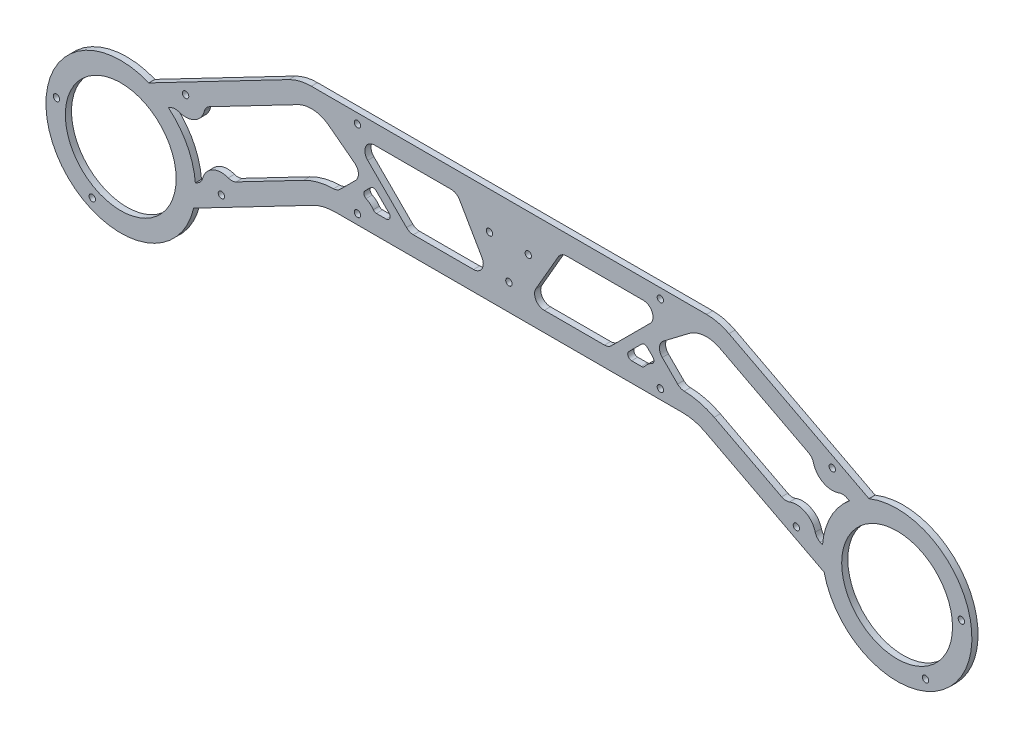
SolidWorks part; units mm, degrees
material "6061-T6 (SS)"
ref_plane "Front Plane" through (0, 0, 0) normal (0, 0, 1) x (1, 0, 0)
ref_plane "Top Plane" through (0, 0, 0) normal (0, 1, 0) x (1, 0, 0)
ref_plane "Right Plane" through (0, 0, 0) normal (1, 0, 0) x (0, 0, -1)
sketch "Sketch1" plane through (0, 0, 0) normal (0, 0, 1) x (1, 0, 0)
  line L0 (-200, -104.1134) -> (0, 0) construction
  line L1 (0, 0) -> (200, -104.1134) construction
  line L2 (-221.4586, -97.3475) -> (-193.2341, -82.6548) construction
  line L3 (-113.3558, -30.8247) -> (-235.4371, -94.3763)
  line L4 (-237.5634, -101.1201) -> (-219.0935, -136.6005)
  line L5 (-212.3497, -138.7268) -> (-101.1208, -80.8247)
  line L6 (-101.8121, -28) -> (101.8121, -28)
  line L7 (0, -28) -> (0, -78) construction
  line L8 (89.5771, -78) -> (-89.5771, -78)
  line L9 (113.3558, -30.8247) -> (235.4371, -94.3763)
  line L10 (237.5634, -101.1201) -> (219.0935, -136.6005)
  line L11 (212.3497, -138.7268) -> (101.1208, -80.8247)
  circle A1 centre (-200, -104.1134) radius 16.05
  circle A2 centre (-221.4586, -97.3475) radius 1.65
  circle A3 centre (-193.2341, -82.6548) radius 1.65
  circle A4 centre (-178.5414, -110.8793) radius 1.65
  circle A5 centre (-206.7659, -125.572) radius 1.65
  arc A6 (-235.4371, -94.3763) -> (-237.5634, -101.1201) centre (-233.1284, -98.8113) ccw
  arc A7 (-219.0935, -136.6005) -> (-212.3497, -138.7268) centre (-214.6584, -134.2918) ccw
  circle A8 centre (0, 0) radius 25 construction
  circle A11 centre (-200, -104.1134) radius 33.55 construction
  circle A12 centre (206.7659, -125.572) radius 1.65
  circle A13 centre (221.4586, -97.3475) radius 1.65
  circle A14 centre (193.2341, -82.6548) radius 1.65
  circle A15 centre (178.5414, -110.8793) radius 1.65
  circle A16 centre (200, -104.1134) radius 16.05
  arc A17 (235.4371, -94.3763) -> (237.5634, -101.1201) centre (233.1284, -98.8113) cw
  arc A18 (219.0935, -136.6005) -> (212.3497, -138.7268) centre (214.6584, -134.2918) cw
  circle A19 centre (-10, -47.2265) radius 1.65
  circle A20 centre (10, -47.2265) radius 1.65
  circle A21 centre (0, -64.547) radius 1.65
  arc A22 (101.1208, -80.8247) -> (89.5771, -78) centre (89.5771, -103) ccw
  arc A23 (113.3558, -30.8247) -> (101.8121, -28) centre (101.8121, -53) ccw
  arc A24 (-113.3558, -30.8247) -> (-101.8121, -28) centre (-101.8121, -53) cw
  arc A25 (-101.1208, -80.8247) -> (-89.5771, -78) centre (-89.5771, -103) cw
  point P17 (-200, -104.1134)
  point P27 (0, -53)
  point P28 (0, -25)
  point P53 (0, -53)
  point P54 (95.6946, -78)
  point P57 (107.9295, -28)
  point P60 (-107.9295, -28)
  point P63 (-95.6946, -78)
  dimension "D1" = 400
  dimension "D3" = 32.1
  dimension "D5" = 3.3
  dimension "D7" = 50
  dimension "D10" = 5
  dimension "D11" = 3.3
  dimension "D12" = 67.1
  dimension "D14" = 3
  dimension "D16" = 25
  dimension "D2" = 125
  dimension "D6" = 45
  dimension "D8" = 3
  dimension "D9" = 50
  dimension "D13" = 50
  dimension "D15" = 20
  dimension "D4" = 4
extrude "Base" add sketch "Sketch1" along normal blind 3.175
sketch "Sketch3" plane through (0, 0, 3.175) normal (0, 0, 1) x (1, 0, 0)
  line L1 (-89.5771, -78) -> (89.5771, -78) construction
  line L2 (-228.3285, -118.8603) -> (-185.7635, -96.7023) construction
  line L3 (101.8121, -28) -> (-101.8121, -28) construction
  line L4 (-237.5634, -101.1201) -> (-219.0935, -136.6005) construction
  line L5 (0, -28) -> (0, -78) construction
  circle A0 centre (-214.6584, -134.2918) radius 1.65
  circle A1 centre (-148.1326, -99.6606) radius 1.65
  circle A2 centre (-78.0312, -73) radius 1.65
  circle A3 centre (-78.0312, -33) radius 1.65
  circle A4 centre (-200, -104.1134) radius 16.05 construction
  circle A5 centre (-166.6026, -64.1802) radius 1.65
  circle A6 centre (-233.1284, -98.8113) radius 1.65
  circle A7 centre (233.1284, -98.8113) radius 1.65
  circle A8 centre (166.6026, -64.1802) radius 1.65
  circle A9 centre (78.0312, -33) radius 1.65
  circle A10 centre (78.0312, -73) radius 1.65
  circle A11 centre (148.1326, -99.6606) radius 1.65
  circle A12 centre (214.6584, -134.2918) radius 1.65
  dimension "D1" = 3.3
  dimension "D3" = 75
  dimension "D6" = 5
  dimension "D4" = 5
  dimension "D5" = 75
  dimension "D2" = 2
extrude "Strut Holes" cut sketch "Sketch3" against normal through all
sketch "Sketch4" plane through (0, 0, 0) normal (0, 0, -1) x (-1, 0, 0)
  line L0 (-166.7326, -103.7062) -> (-160.3585, -100.3881)
  line L1 (-101.1208, -80.8247) -> (-212.3497, -138.7268) construction
  line L2 (-140.5243, -90.063) -> (-105.7383, -71.9546)
  line L3 (-86.9223, -66.5452) -> (-79.0095, -58.6325)
  line L4 (-79.5169, -51.1182) -> (-92.7277, -41.0638)
  line L5 (-180.585, -77.0959) -> (-174.2109, -73.7777)
  line L6 (-235.4371, -94.3763) -> (-113.3558, -30.8247) construction
  line L7 (-154.3768, -63.4527) -> (-108.7383, -39.6948)
  line L8 (89.5771, -78) -> (-89.5771, -78) construction
  line L9 (-68.2844, -68) -> (-63.1994, -68)
  line L10 (-61.7852, -64.5858) -> (-68.4242, -57.9467)
  line L11 (-71.2527, -57.9467) -> (-74.1321, -60.8262)
  line L12 (-25.4306, -40.5) -> (-13.8835, -60.5)
  line L13 (-18.2137, -68) -> (-49.2288, -68)
  line L14 (-52.7643, -66.5355) -> (-72.7643, -46.5355)
  line L15 (-69.2288, -38) -> (-29.7607, -38)
  line L16 (-101.8121, -28) -> (101.8121, -28) construction
  line L17 (0, -28) -> (0, -78) construction
  line L18 (52.7643, -66.5355) -> (72.7643, -46.5355)
  line L19 (18.2137, -68) -> (49.2288, -68)
  line L20 (25.4306, -40.5) -> (13.8835, -60.5)
  line L21 (69.2288, -38) -> (29.7607, -38)
  line L22 (68.2844, -68) -> (63.1994, -68)
  line L23 (61.7852, -64.5858) -> (68.4242, -57.9467)
  line L24 (71.2527, -57.9467) -> (74.1321, -60.8262)
  line L25 (154.3768, -63.4527) -> (108.7383, -39.6948)
  line L26 (180.585, -77.0959) -> (174.2109, -73.7777)
  line L27 (166.7326, -103.7062) -> (160.3585, -100.3881)
  line L28 (140.5243, -90.063) -> (105.7383, -71.9546)
  line L29 (86.9223, -66.5452) -> (79.0095, -58.6325)
  line L30 (79.5169, -51.1182) -> (92.7277, -41.0638)
  arc A0 (-182.112, -88.1128) -> (-176.6329, -98.638) centre (-200, -104.1134) cw
  arc A1 (-174.0237, -101.958) -> (-172.208, -103.1405) centre (-178.5414, -110.8793) cw
  arc A2 (-183.3349, -84.0711) -> (-183.2622, -81.9056) centre (-193.2341, -82.6548) ccw
  arc A3 (-157.8223, -97.1889) -> (-144.5996, -90.3055) centre (-148.1326, -99.6606) cw
  arc A4 (-105.7383, -71.9546) -> (-90.3477, -68.0085) centre (-89.5771, -103) cw
  arc A5 (-89.5771, -78) -> (-101.1208, -80.8247) centre (-89.5771, -103) ccw construction
  arc A6 (-170.1356, -73.5353) -> (-156.9129, -66.6519) centre (-166.6026, -64.1802) ccw
  arc A7 (-108.7383, -39.6948) -> (-92.7277, -41.0638) centre (-101.8121, -53) cw
  arc A8 (-101.8121, -28) -> (-113.3558, -30.8247) centre (-101.8121, -53) ccw construction
  arc A9 (-69.9089, -67.1667) -> (-73.6035, -64.0337) centre (-78.0312, -73) ccw
  circle A10 centre (-10, -47.2265) radius 10 construction
  circle A11 centre (0, -64.547) radius 10 construction
  arc A12 (-156.9129, -66.6519) -> (-154.3768, -63.4527) centre (-152.068, -67.8878) cw
  arc A13 (-174.2109, -73.7777) -> (-170.1356, -73.5353) centre (-171.9022, -78.2128) cw
  arc A14 (-183.2622, -81.9056) -> (-180.585, -77.0959) centre (-178.2763, -81.5309) cw
  arc A15 (-182.112, -88.1128) -> (-183.3349, -84.0711) centre (-178.3853, -84.7793) cw
  arc A16 (-176.6329, -98.638) -> (-174.0237, -101.958) centre (-171.7648, -97.4973) ccw
  arc A17 (-172.208, -103.1405) -> (-166.7326, -103.7062) centre (-169.0413, -99.2712) ccw
  arc A18 (-160.3585, -100.3881) -> (-157.8223, -97.1889) centre (-162.6672, -95.953) ccw
  arc A19 (-144.5996, -90.3055) -> (-140.5243, -90.063) centre (-142.833, -85.628) ccw
  arc A20 (-79.0095, -58.6325) -> (-79.5169, -51.1182) centre (-82.545, -55.0969) ccw
  arc A21 (-90.3477, -68.0085) -> (-86.9223, -66.5452) centre (-90.4578, -63.0097) ccw
  arc A22 (-49.2288, -68) -> (-52.7643, -66.5355) centre (-49.2288, -63) cw
  arc A23 (-25.4306, -40.5) -> (-29.7607, -38) centre (-29.7607, -43) ccw
  arc A24 (-13.8835, -60.5) -> (-18.2137, -68) centre (-18.2137, -63) cw
  arc A25 (-72.7643, -46.5355) -> (-69.2288, -38) centre (-69.2288, -43) cw
  arc A26 (-68.4242, -57.9467) -> (-71.2527, -57.9467) centre (-69.8385, -59.3609) ccw
  arc A27 (-68.2844, -68) -> (-69.9089, -67.1667) centre (-68.2844, -66) cw
  arc A28 (-74.1321, -60.8262) -> (-73.6035, -64.0337) centre (-72.7179, -62.2404) ccw
  arc A29 (-63.1994, -68) -> (-61.7852, -64.5858) centre (-63.1994, -66) ccw
  arc A30 (49.2288, -68) -> (52.7643, -66.5355) centre (49.2288, -63) ccw
  arc A31 (13.8835, -60.5) -> (18.2137, -68) centre (18.2137, -63) ccw
  arc A32 (25.4306, -40.5) -> (29.7607, -38) centre (29.7607, -43) cw
  arc A33 (72.7643, -46.5355) -> (69.2288, -38) centre (69.2288, -43) ccw
  arc A34 (63.1994, -68) -> (61.7852, -64.5858) centre (63.1994, -66) cw
  arc A35 (68.4242, -57.9467) -> (71.2527, -57.9467) centre (69.8385, -59.3609) cw
  arc A36 (68.2844, -68) -> (69.9089, -67.1667) centre (68.2844, -66) ccw
  arc A37 (74.1321, -60.8262) -> (73.6035, -64.0337) centre (72.7179, -62.2404) cw
  arc A38 (69.9089, -67.1667) -> (73.6035, -64.0337) centre (78.0312, -73) cw
  arc A39 (156.9129, -66.6519) -> (154.3768, -63.4527) centre (152.068, -67.8878) ccw
  arc A40 (170.1356, -73.5353) -> (156.9129, -66.6519) centre (166.6026, -64.1802) cw
  arc A41 (174.2109, -73.7777) -> (170.1356, -73.5353) centre (171.9022, -78.2128) ccw
  arc A42 (183.2622, -81.9056) -> (180.585, -77.0959) centre (178.2763, -81.5309) ccw
  arc A43 (183.3349, -84.0711) -> (183.2622, -81.9056) centre (193.2341, -82.6548) cw
  arc A44 (182.112, -88.1128) -> (183.3349, -84.0711) centre (178.3853, -84.7793) ccw
  arc A45 (182.112, -88.1128) -> (176.6329, -98.638) centre (200, -104.1134) ccw
  arc A46 (176.6329, -98.638) -> (174.0237, -101.958) centre (171.7648, -97.4973) cw
  arc A47 (174.0237, -101.958) -> (172.208, -103.1405) centre (178.5414, -110.8793) ccw
  arc A48 (172.208, -103.1405) -> (166.7326, -103.7062) centre (169.0413, -99.2712) cw
  arc A49 (160.3585, -100.3881) -> (157.8223, -97.1889) centre (162.6672, -95.953) cw
  arc A50 (157.8223, -97.1889) -> (144.5996, -90.3055) centre (148.1326, -99.6606) ccw
  arc A51 (144.5996, -90.3055) -> (140.5243, -90.063) centre (142.833, -85.628) cw
  arc A52 (105.7383, -71.9546) -> (90.3477, -68.0085) centre (89.5771, -103) ccw
  arc A53 (90.3477, -68.0085) -> (86.9223, -66.5452) centre (90.4578, -63.0097) cw
  arc A54 (79.0095, -58.6325) -> (79.5169, -51.1182) centre (82.545, -55.0969) cw
  arc A55 (108.7383, -39.6948) -> (92.7277, -41.0638) centre (101.8121, -53) ccw
  point P75 (-74.9619, -54.5849)
  point P78 (-88.3969, -68.0199)
  point P91 (-69.3709, -68)
  point P96 (-58.3709, -68)
  dimension "D1" = 24
  dimension "D2" = 10
  dimension "D4" = 10
  dimension "D5" = 11.5
  dimension "D6" = 5
  dimension "D10" = 2.2457
  dimension "D15" = 5
  dimension "D16" = 5
  dimension "D17" = 2
  dimension "D3" = 10
  dimension "45" = 45
  dimension "D7" = 11.5
  dimension "D8" = 10
  dimension "D9" = 45
  dimension "D11" = 19
  dimension "D12" = 11
  dimension "D13" = 10
  dimension "D14" = 10
extrude "Lightening Holes" cut sketch "Sketch4" against normal through all
sketch "Sketch5" plane through (0, 0, 0) normal (0, 0, -1) x (-1, 0, 0)
  circle A0 centre (-200, -104.1134) radius 28.55
  circle A1 centre (-200, -104.1134) radius 38.55
  circle A2 centre (-233.1284, -98.8113) radius 1.65 construction
  circle A3 centre (-214.6584, -134.2918) radius 1.65 construction
  circle A4 centre (-233.1284, -98.8113) radius 1.65
  circle A5 centre (-214.6584, -134.2918) radius 1.65
  dimension "D1" = 57.1
  dimension "D2" = 10
extrude "Inner Mod Boss" add sketch "Sketch5" against normal up to surface (3.175 mm away) up to face at (144.3427, -77.7595, 3.175)
extrude "Inner Mod Cut" cut sketch "Sketch5<2>" against normal through all contours A0 region at (200, -104.1134, 0)
sketch "Sketch5<2>" plane through (0, 0, 0) normal (0, 0, -1) x (-1, 0, 0) same geometry as "Sketch5"
mirror "Mirror1" about plane through (0, 0, 0) normal (1, 0, 0) of "Inner Mod Cut", "Inner Mod Boss"
